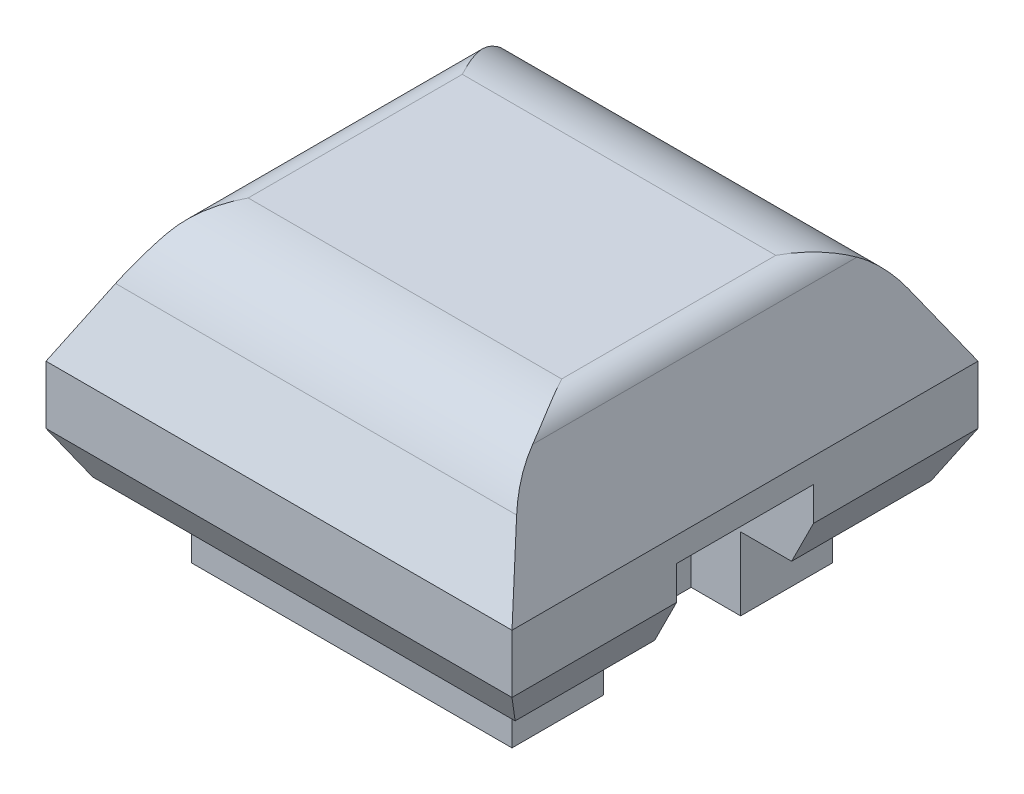
SolidWorks part; units mm, degrees
ref_plane "Front Plane" through (0, 0, 0) normal (0, 0, 1) x (1, 0, 0)
ref_plane "Top Plane" through (0, 0, 0) normal (0, 1, 0) x (1, 0, 0)
ref_plane "Right Plane" through (0, 0, 0) normal (1, 0, 0) x (0, 0, -1)
sketch "Sketch1" plane through (0, 0, 0) normal (0, 0, 1) x (1, 0, 0)
  line L0 (-80, 0) -> (80, 0)
  line L1 (80, 0) -> (62.7639, 34.4721)
  line L2 (53.8197, 40) -> (-53.8197, 40)
  line L3 (-62.7639, 34.4721) -> (-80, 0)
  line L4 (0, 129.2056) -> (0, -132.4766) construction
  line L5 (-132.9298, -10) -> (167.1321, -10) construction
  line L6 (-62.7639, -54.4721) -> (-80, -20)
  line L7 (53.8197, -60) -> (-53.8197, -60)
  line L8 (80, -20) -> (62.7639, -54.4721)
  line L9 (-80, -20) -> (80, -20)
  arc A0 (62.7639, 34.4721) -> (53.8197, 40) centre (53.8197, 30) ccw
  arc A1 (-53.8197, 40) -> (-62.7639, 34.4721) centre (-53.8197, 30) ccw
  arc A2 (-53.8197, -60) -> (-62.7639, -54.4721) centre (-53.8197, -50) cw
  arc A3 (62.7639, -54.4721) -> (53.8197, -60) centre (53.8197, -50) cw
  point P9 (60, 40)
  point P12 (-60, 40)
  point P23 (-60, -60)
  point P24 (60, -60)
  dimension "D4" = 10
  dimension "D1" = 40
  dimension "D2" = 160
  dimension "D3" = 120
  dimension "D5" = 10
extrude "Boss-Extrude1" add sketch "Sketch1" along normal blind 80 and the other way blind 80
sketch "Sketch2" plane through (0, 0, 0) normal (1, 0, 0) x (0, 0, -1)
  line L0 (-177.9739, -10) -> (184.9396, -10) construction
  line L1 (67.2536, 22.3062) -> (80, 0)
  line L2 (80, 0) -> (-80, 0) construction
  line L3 (-67.2536, 22.3062) -> (-80, 0)
  line L4 (0, 129.2056) -> (0, -10) construction
  line L5 (-80, 0) -> (-80, 40)
  line L6 (-36.764, 40) -> (-17.8112, 40) construction
  line L7 (-80, 40) -> (-36.764, 40)
  line L8 (80, 0) -> (80, 40)
  line L9 (80, 40) -> (36.764, 40)
  line L10 (80, 40) -> (-80, 40) construction
  line L11 (80, -60) -> (36.764, -60)
  line L12 (80, -20) -> (80, -60)
  line L13 (67.2536, -42.3062) -> (80, -20)
  line L14 (-67.2536, -42.3062) -> (-80, -20)
  line L15 (-80, -20) -> (-80, -60)
  line L16 (-80, -60) -> (-36.764, -60)
  arc A0 (67.2536, 22.3062) -> (36.764, 40) centre (36.764, 4.8836) ccw
  arc A1 (-67.2536, 22.3062) -> (-36.764, 40) centre (-36.764, 4.8836) cw
  arc A2 (67.2536, -42.3062) -> (36.764, -60) centre (36.764, -24.8836) cw
  arc A3 (-67.2536, -42.3062) -> (-36.764, -60) centre (-36.764, -24.8836) ccw
  dimension "D1" = 10
extrude "Cut-Extrude2" cut sketch "Sketch2" against normal through all both and the other way through all
sketch "Sketch3" plane through (0, 0, 0) normal (0, -1, 0) x (1, 0, 0)
  line L1 (-80, -80) -> (-80, 80) construction
  line L2 (-80, 80) -> (80, 80) construction
  line L3 (80, -80) -> (80, 80) construction
  line L4 (-71.3004, -80) -> (71.3004, -80)
  line L5 (-80, -80) -> (-80, 80)
  line L6 (-80, 80) -> (80, 80)
  line L7 (80, -80) -> (80, 80)
  line L8 (80, -80) -> (71.3004, -80)
  line L9 (-71.3004, -80) -> (-80, -80)
extrude "Boss-Extrude2" add sketch "Sketch3" along normal blind 20
ref_plane "Plane1" through (0, -60, 0) normal (0, -1, 0) x (-1, 0, 0)
sketch "Sketch6" plane through (0, -60, 0) normal (0, -1, 0) x (-1, 0, 0)
  line L1 (80, -80) -> (-80, -80)
  line L2 (-80, -80) -> (-80, 80)
  line L3 (-80, 80) -> (80, 80)
  line L4 (80, 80) -> (80, -80)
  line L5 (-80, -80) -> (80, -80) construction
  line L6 (80, -80) -> (80, 80) construction
  line L7 (80, 80) -> (-80, 80) construction
  line L8 (-80, 80) -> (-80, -80) construction
extrude "Cut-Extrude3" cut sketch "Sketch6" against normal blind 25
sketch "Sketch7" plane through (0, -60, 0) normal (0, -1, 0) x (-1, 0, 0)
  line L1 (55, -55) -> (-55, -55)
  line L2 (55, -55) -> (55, 55)
  line L3 (55, 55) -> (-55, 55)
  line L4 (-55, -55) -> (-55, 55)
  line L5 (0, 55) -> (0, -55) construction
  line L6 (55, 0) -> (-55, 0) construction
  point P0 (0, 0)
  dimension "D1" = 110
  dimension "D2" = 110
extrude "Boss-Extrude3" add sketch "Sketch7" against normal up to surface (25 mm away) up to face at (0, -35, 0)
sketch "Sketch8" plane through (0, -60, 0) normal (0, -1, 0) x (-1, 0, 0)
  line L1 (37, -37) -> (-37, -37) construction
  line L2 (37, -37) -> (37, 37) construction
  line L3 (37, 37) -> (-37, 37) construction
  line L4 (-37, -37) -> (-37, 37) construction
  line L5 (0, 37) -> (0, -37) construction
  line L6 (37, 0) -> (-37, 0) construction
  circle A0 centre (-37, -37) radius 2
  circle A1 centre (-37, 37) radius 2
  circle A2 centre (37, 37) radius 2
  circle A3 centre (37, -37) radius 2
  point P0 (0, 0)
  point P14 (0, 0)
  dimension "D3" = 4
  dimension "D1" = 74
  dimension "D2" = 74
  dimension "D4" = 4
extrude "Cut-Extrude4" cut sketch "Sketch8" against normal up to surface (25 mm away) up to face at (0, -35, 0)
sketch "Sketch9" plane through (80, 0, 0) normal (1, 0, 0) x (0, 0, -1)
  line L0 (0, 0) -> (0, -74.9113) construction
  line L1 (-23.5, -8.4289) -> (23.5, -8.4289)
  line L2 (-23.5, -8.4289) -> (-23.5, -60)
  line L3 (-23.5, -60) -> (23.5, -60)
  line L4 (23.5, -8.4289) -> (23.5, -60)
  line L7 (55, -60) -> (-55, -60) construction
  dimension "D1" = 23.5
  dimension "D2" = 23.5
extrude "Cut-Extrude5" cut sketch "Sketch9" against normal blind 42
sketch "Sketch10" plane through (0, -8.4289, 0) normal (0, -1, 0) x (1, 0, 0)
  line L0 (80, 0) -> (38, 0) construction
  line L1 (80, -23.5) -> (80, 23.5) construction
  line L6 (38, -23.5) -> (38, 23.5) construction
  circle A0 centre (49.5, 0) radius 7.5
  point P6 (49.5, 0)
  point P10 (57, 0)
  dimension "D2" = 15
  dimension "D1" = 30.5
  dimension "D3" = 23
extrude "Boss-Extrude4" add sketch "Sketch10" along normal blind 10
